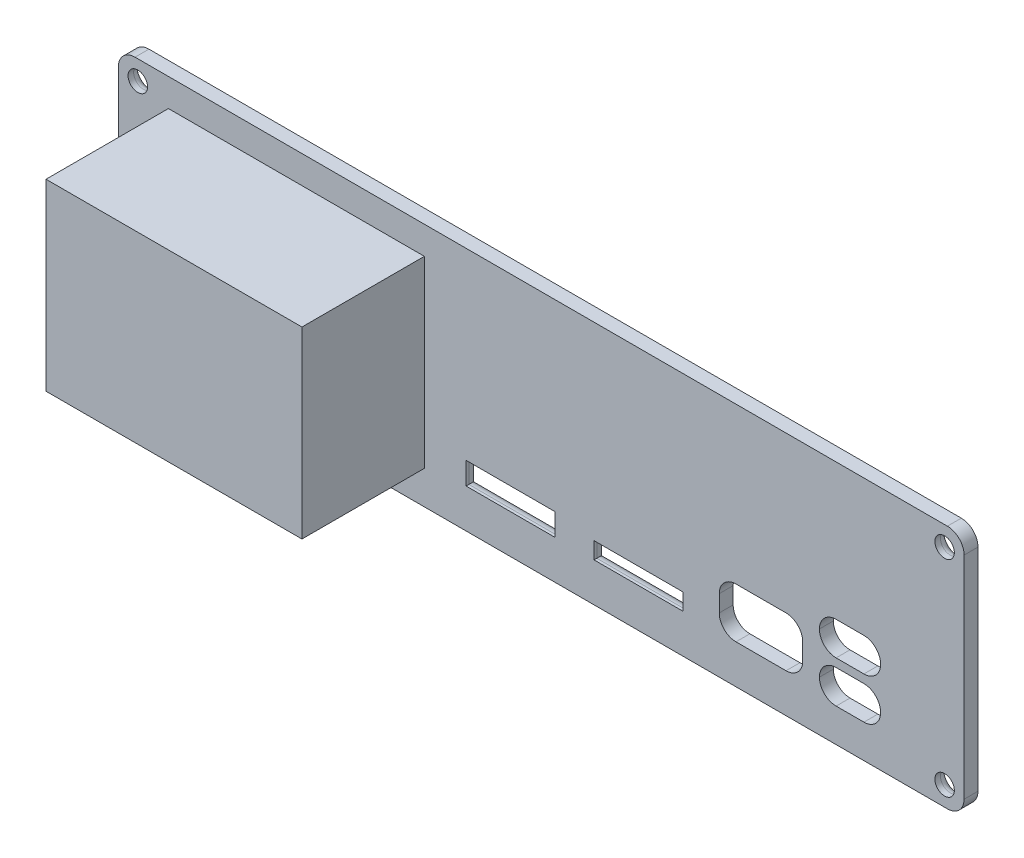
SolidWorks part; units mm, degrees
ref_plane "Front Plane" through (0, 0, 0) normal (0, 0, 1) x (1, 0, 0)
ref_plane "Top Plane" through (0, 0, 0) normal (0, 1, 0) x (1, 0, 0)
ref_plane "Right Plane" through (0, 0, 0) normal (1, 0, 0) x (0, 0, -1)
sketch "Sketch1" plane through (0, 0, 0) normal (0, 0, 1) x (1, 0, 0)
  line L1 (76, -22) -> (-76, -22)
  line L2 (76, -22) -> (76, 22)
  line L3 (76, 22) -> (-76, 22)
  line L4 (-76, -22) -> (-76, 22)
  line L5 (76, -22) -> (-76, 22) construction
  line L6 (76, 22) -> (-76, -22) construction
  point P0 (0, 0)
  dimension "D1" = 152
  dimension "D2" = 44
extrude "main_body" add sketch "Sketch1" along normal blind 2.5
fillet "body_corners" radius 3 4 edges at (-76, -22, 1.25) (76, -22, 1.25) (76, 22, 1.25) (-76, 22, 1.25)
sketch "Sketch2" plane through (0, 0, 2.5) normal (0, 0, 1) x (1, 0, 0)
  line L0 (-76, 18.5) -> (76, 18.5) construction
  line L1 (-76, 19) -> (-76, -19) construction
  line L2 (76, -19) -> (76, 19) construction
  line L3 (-72.5, 22) -> (-72.5, -22) construction
  line L4 (-76, -18.5) -> (76, -18.5) construction
  line L8 (73, 22) -> (-73, 22) construction
  line L9 (72.5, 22) -> (72.5, -22) construction
  line L10 (-73, -22) -> (73, -22) construction
  circle A1 centre (-72.5, -18.5) radius 1.75
  circle A2 centre (72.5, 18.5) radius 1.75
  circle A3 centre (72.5, -18.5) radius 1.75
  circle A4 centre (-72.5, 18.5) radius 1.75
  dimension "D5" = 3.5
  dimension "D6" = 3.5
  dimension "D7" = 3.5
  dimension "D8" = 3.5
  dimension "D1" = 3.5
  dimension "D2" = 3.5
  dimension "D3" = 3.5
  dimension "D4" = 3.5
extrude "mounting_holes" cut sketch "Sketch2" against normal through all
fillet "bolt_heads" radius 1.5 4 edges at (-70.75, -18.5, 0) (-70.75, 18.5, 0) (74.25, -18.5, 0) (74.25, 18.5, 0)
sketch "Sketch3" plane through (0, 0, 2.5) normal (0, 0, 1) x (1, 0, 0)
  line L0 (-76, 5) -> (76, 5) construction
  line L1 (-76, 19) -> (-76, -19) construction
  line L2 (76, -19) -> (76, 19) construction
  line L3 (73, 22) -> (-73, 22) construction
  line L4 (-73, -22) -> (73, -22) construction
  line L5 (0, 22) -> (0, -22) construction
  line L6 (76, -19) -> (76, 19) construction
  line L8 (50, -2.5) -> (61, -2.5)
  line L10 (50, -2.5) -> (50, -8.5)
  line L11 (50, -8.5) -> (61, -8.5)
  line L13 (61, -2.5) -> (61, -8.5)
  line L14 (50, -2.5) -> (61, -8.5) construction
  line L16 (50, -8.5) -> (61, -2.5) construction
  line L17 (32, -6) -> (47, -6)
  line L18 (32, -6) -> (32, -15)
  line L19 (32, -15) -> (47, -15)
  line L20 (47, -6) -> (47, -15)
  line L21 (32, -6) -> (47, -15) construction
  line L22 (32, -15) -> (47, -6) construction
  line L23 (50, -10) -> (61, -10)
  line L24 (50, -10) -> (50, -16)
  line L25 (50, -16) -> (61, -16)
  line L26 (61, -10) -> (61, -16)
  line L27 (50, -10) -> (61, -16) construction
  line L28 (50, -16) -> (61, -10) construction
  line L29 (9.5, -12) -> (25.5, -12)
  line L30 (9.5, -12) -> (9.5, -15)
  line L31 (9.5, -15) -> (25.5, -15)
  line L32 (25.5, -12) -> (25.5, -15)
  line L33 (9.5, -12) -> (25.5, -15) construction
  line L34 (9.5, -15) -> (25.5, -12) construction
  line L35 (-13.5, -11) -> (2.5, -11)
  line L36 (-13.5, -11) -> (-13.5, -15)
  line L37 (-13.5, -15) -> (2.5, -15)
  line L38 (2.5, -11) -> (2.5, -15)
  line L39 (-13.5, -11) -> (2.5, -15) construction
  line L40 (-13.5, -15) -> (2.5, -11) construction
  point P15 (-5.5, -13)
  point P34 (55.5, -13)
  point P36 (55.5, -5.5)
  point P41 (39.5, -10.5)
  point P49 (55.5, -16)
  point P51 (17.5, -13.5)
  dimension "D7" = 73.5
  dimension "D8" = 7
  dimension "D9" = 4
  dimension "D10" = 16
  dimension "D12" = 50.5
  dimension "D13" = 6
  dimension "D14" = 11
  dimension "D15" = 29
  dimension "D1" = 17
  dimension "D16" = 6
  dimension "D17" = 15
  dimension "D18" = 15
  dimension "D19" = 11
  dimension "D20" = 6
  dimension "D21" = 15
  dimension "D22" = 9
  dimension "D23" = 7.5
  dimension "D25" = 13.5
  dimension "D26" = 7
  dimension "D28" = 7
  dimension "D30" = 3
  dimension "D31" = 16
extrude "connectors" cut sketch "Sketch3" against normal through all
fillet "usb_host_corners" radius 3 4 edges at (47, -15, 1.25) (47, -6, 1.25) (32, -15, 1.25) (32, -6, 1.25)
fillet "usb_dfu_corners" radius 3 8 edges at (61, -2.5, 1.25) (61, -8.5, 1.25) (50, -8.5, 1.25) (50, -2.5, 1.25) (61, -10, 1.25) (61, -16, 1.25) (50, -16, 1.25) (50, -10, 1.25)
fillet "Fillet1" radius 2 8 edges at (-5.5, -11, 0) (-13.5, -13, 0) (-5.5, -15, 0) (2.5, -13, 0) (9.5, -13.5, 0) (25.5, -13.5, 0) (17.5, -15, 0) (17.5, -12, 0)
sketch "Sketch4" plane through (0, 0, 2.5) normal (0, 0, 1) x (1, 0, 0)
  line L0 (-76, 19) -> (-76, -19) construction
  line L1 (-67, 17) -> (-21, 17)
  line L2 (-67, 17) -> (-67, -16)
  line L3 (-67, -16) -> (-21, -16)
  line L4 (-21, 17) -> (-21, -16)
  line L5 (-67, 17) -> (-21, -16) construction
  line L6 (-67, -16) -> (-21, 17) construction
  line L7 (-73, -22) -> (73, -22) construction
  point P0 (-44, 0.5)
  dimension "D1" = 9
  dimension "D2" = 6
  dimension "D3" = 33
  dimension "D4" = 46
extrude "keyer" add sketch "Sketch4" along normal blind 22
sketch "Sketch5" plane through (0, 0, 24.5) normal (0, 0, 1) x (1, 0, 0)
  line L0 (-67, -16) -> (-21, 17) construction
  line L1 (-21, 17) -> (-67, 17) construction
  line L2 (-22, -15) -> (-66, -15)
  line L3 (-67, 17) -> (-21, -16) construction
  line L4 (-22, -15) -> (-22, 16)
  line L5 (-22, 16) -> (-66, 16)
  line L6 (-66, -15) -> (-66, 16)
  line L7 (-22, -15) -> (-66, 16) construction
  line L8 (-22, 16) -> (-66, -15) construction
  line L9 (-21, -16) -> (-21, 17) construction
  point P4 (-44, 0.5)
  dimension "D1" = 1
  dimension "D2" = 1
extrude "keyer_cut" cut sketch "Sketch5" against normal through all from offset 1 offset against normal yes
